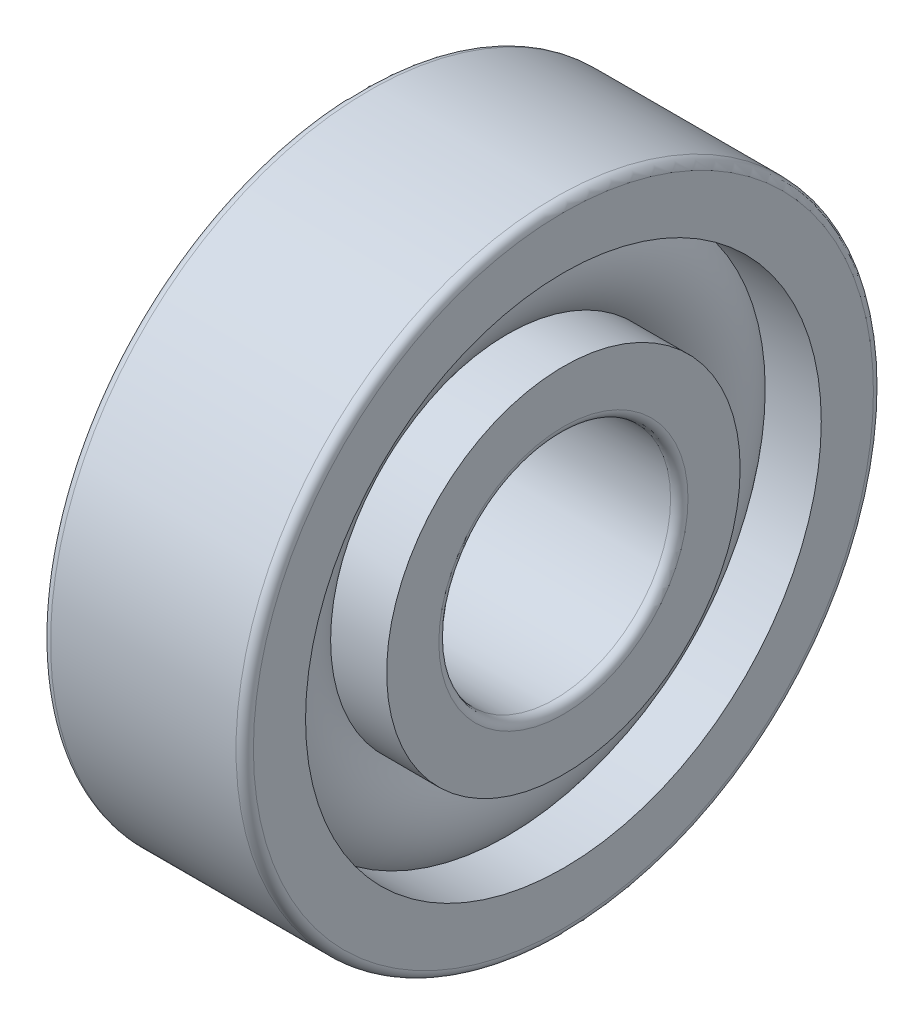
SolidWorks part; units mm, degrees
ref_plane "Plane1" through (0, 0, 0) normal (0, 0, 1) x (1, 0, 0)
ref_plane "Plane2" through (0, 0, 0) normal (0, 1, 0) x (1, 0, 0)
ref_plane "Plane3" through (0, 0, 0) normal (1, 0, 0) x (0, 0, -1)
sketch "Clipboard" plane through (0, 0, 0) normal (0, 0, 1) x (1, 0, 0)
  line L0 (-10, 0) -> (10, 0) construction
  line L1 (0, 0) -> (22.3471, -0.7804)
  line L2 (0, 0) -> (7.4954, 0.2617)
  line L3 (0, 0) -> (22.3471, -0.7804)
  line L4 (0, 0) -> (-22.3573, -0.3902)
  dimension "BallCLRad" = 7.5
  dimension "Count" = 2
  dimension "Show_count" = 2
  dimension "Max_count" = 2
  dimension "Min_count" = 1
sketch "CagSpiSke" plane through (0, 0, 0) normal (0, 0, 1) x (1, 0, 0)
  line L0 (0.21, 7.15) -> (0.21, 7.85)
  line L1 (0.21, 7.85) -> (-0.21, 7.85)
  line L2 (-0.21, 7.85) -> (-0.21, 7.15)
  line L3 (-0.21, 7.15) -> (0.21, 7.15)
  line L4 (-20.6375, 0) -> (20.6375, 0) construction
  line L5 (0, 0) -> (0, 23.7692) construction
  dimension "Thickness" = 0.42
  dimension "OD" = 15.7
  dimension "ID" = 14.3
revolve "CageSpine" add sketch "CagSpiSke" angle 0.001 about L4 reverse direction yes
ref_axis "Axis1" through (-50, 0, 0) along (1, 0, 0)
sketch "CagBalSke" plane through (0, 0, 0) normal (0, 0, 1) x (1, 0, 0)
  line L0 (-2.31, 7.5) -> (2.31, 7.5)
  line L1 (-1.905, 7.5) -> (1.905, 7.5) construction
  line L2 (-10, 0) -> (10, 0) construction
  line L3 (0, 0) -> (0, 24) construction
  arc A0 (2.31, 7.5) -> (-2.31, 7.5) centre (0, 7.5) cw
  dimension "CageWallOD" = 4.62
  dimension "BallCLRad" = 7.5
revolve "CageBall" [suppressed] add sketch "CagBalSke" angle 360 about L1 reverse direction yes
pattern_circular "CageBalls" [suppressed] count 2 every 180 about axis through (-50, 0, 0) along (1, 0, 0)
sketch "CagTrmODSke" plane through (0, 0, 0) normal (0, 0, 1) x (1, 0, 0)
  line L0 (2.311, 7.85) -> (2.311, 9.811)
  line L1 (2.311, 9.811) -> (-2.311, 9.811)
  line L2 (-2.311, 9.811) -> (-2.311, 7.85)
  line L3 (-2.311, 7.85) -> (2.311, 7.85)
  line L4 (-20.6375, 0) -> (20.6375, 0) construction
  line L5 (0, 0) -> (0, 25) construction
  dimension "Width" = 4.622
  dimension "ID" = 15.7
  dimension "OD" = 19.622
revolve "CageTrimOD" [suppressed] cut sketch "CagTrmODSke" angle 360 about L4 reverse direction yes
sketch "CagTrmIDSke" plane through (0, 0, 0) normal (0, 0, 1) x (1, 0, 0)
  line L0 (2.311, 5.191) -> (2.311, 7.15)
  line L1 (2.311, 7.15) -> (-2.311, 7.15)
  line L2 (-2.311, 7.15) -> (-2.311, 5.191)
  line L3 (-2.311, 5.191) -> (2.311, 5.191)
  line L4 (-20.6375, 0) -> (20.6375, 0) construction
  line L5 (0, 0) -> (0, 25) construction
  dimension "ID" = 10.382
  dimension "OD" = 14.3
  dimension "Width" = 4.622
revolve "CageTrimID" [suppressed] cut sketch "CagTrmIDSke" angle 360 about L4 reverse direction yes
sketch "BalSimSke" plane through (0, 0, 0) normal (0, 0, 1) x (1, 0, 0)
  line L0 (-10, 0) -> (10, 0) construction
  line L1 (-10, 7.5) -> (10, 7.5) construction
  line L2 (0, 0) -> (0, 23) construction
  circle A0 centre (0, 7.5) radius 2.1
  dimension "Ball_diameter" = 4.2
  dimension "BallCLRad" = 7.5
revolve "BallsSimplified" add sketch "BalSimSke" angle 360 about L0
sketch "BalDetSke" plane through (0, 0, 0) normal (0, 0, 1) x (1, 0, 0)
  line L0 (-2.1, 7.5) -> (2.1, 7.5)
  line L1 (-1.905, 7.5) -> (1.905, 7.5) construction
  line L2 (0, 0) -> (0, 25) construction
  arc A0 (2.1, 7.5) -> (-2.1, 7.5) centre (0, 7.5) cw
  dimension "Ball_diameter" = 4.2
  dimension "BallCLRad" = 7.5
revolve "BallDetailed" [suppressed] add sketch "BalDetSke" angle 360 about L1 reverse direction yes
sketch "InnRacSke" plane through (0, 0, 0) normal (0, 0, 1) x (1, 0, 0)
  line L0 (-1.5315, 6.1) -> (-3.5, 6.1)
  line L1 (-3.5, 6.1) -> (-3.5, 4.3)
  line L2 (-3.2, 4) -> (3.2, 4)
  line L3 (3.5, 4.3) -> (3.5, 6.1)
  line L4 (3.5, 6.1) -> (1.5315, 6.1)
  line L5 (-20.6375, 0) -> (20.6375, 0) construction
  line L6 (0, 0) -> (0, 30) construction
  arc A0 (-3.5, 4.3) -> (-3.2, 4) centre (-3.2, 4.3) ccw
  arc A1 (3.2, 4) -> (3.5, 4.3) centre (3.2, 4.3) ccw
  arc A2 (1.5315, 6.1) -> (-1.5315, 6.1) centre (0, 7.5) cw
  dimension "Fillet_radius" = 0.3
  dimension "Ball_diameter" = 4.15
  dimension "ID" = 8
  dimension "OD" = 12.2
  dimension "Width" = 7
  dimension "BallCLRad" = 7.5
revolve "InnerRace" add sketch "InnRacSke" angle 360 about L5 reverse direction yes
sketch "OutRacSke" plane through (0, 0, 0) normal (0, 0, 1) x (1, 0, 0)
  line L0 (-1.5315, 8.9) -> (-3.5, 8.9)
  line L1 (-3.5, 8.9) -> (-3.5, 10.7)
  line L2 (-3.2, 11) -> (3.2, 11)
  line L3 (3.5, 10.7) -> (3.5, 8.9)
  line L4 (3.5, 8.9) -> (1.5315, 8.9)
  line L5 (-20.6375, 0) -> (20.6375, 0) construction
  line L6 (0, 0) -> (0, 30) construction
  arc A0 (-3.5, 10.7) -> (-3.2, 11) centre (-3.2, 10.7) cw
  arc A1 (3.2, 11) -> (3.5, 10.7) centre (3.2, 10.7) cw
  arc A2 (1.5315, 8.9) -> (-1.5315, 8.9) centre (0, 7.5) ccw
  dimension "Fillet_radius" = 0.3
  dimension "Ball_diameter" = 4.15
  dimension "OD" = 22
  dimension "ID" = 17.8
  dimension "Width" = 7
  dimension "BallCLRad" = 7.5
revolve "OuterRace" add sketch "OutRacSke" angle 360 about L5 reverse direction yes
pattern_circular "BallsDetailed" [suppressed] count 2 every 180 about axis through (-50, 0, 0) along (1, 0, 0)
equation "\"BallCLRad@Clipboard\" = ( \"OD@OutRacSke\" + \"ID@InnRacSke\" ) / 4"
equation "\"BallCLRad@BalSimSke\" = \"BallCLRad@Clipboard\""
equation "\"BallCLRad@BalDetSke\" = \"BallCLRad@Clipboard\""
equation "\"BallCLRad@InnRacSke\" = \"BallCLRad@Clipboard\""
equation "\"BallCLRad@OutRacSke\" = \"BallCLRad@Clipboard\""
equation "\"Ball_diameter@InnRacSke\" = \"Ball_diameter@BalDetSke\" - 0.05"
equation "\"Ball_diameter@OutRacSke\" = \"Ball_diameter@BalDetSke\" - 0.05"
equation "\"Ball_diameter@BalSimSke\" = \"Ball_diameter@BalDetSke\""
equation "\"Width@OutRacSke\" = \"Width@InnRacSke\""
equation "\"Fillet_radius@OutRacSke\" = \"Fillet_radius@InnRacSke\""
equation "\"Max_count@Clipboard\" = int( 3.14159265 / atn(( \"Ball_diameter@BalDetSke\" / 2) / sqr( \"BallCLRad@Clipboard\"  *  \"BallCLRad@Clipboard\" - ( \"Ball_diameter@BalDetSke\" / 2) *  ( \"Ball_diameter@BalDetSke\" / 2))))"
equation "\"Max_count@Clipboard\" = ((sgn( \"Max_count@Clipboard\" - \"Count@Clipboard\" )-1)*( \"Max_count@Clipboard\" - \"Count@Clipboard\" ))/-2+ \"Count@Clipboard\""
equation "\"Count@BallsDetailed\" = int( \"Show_count@Clipboard\" ) "
equation "\"Count@BallsDetailed\" = ((sgn( \"Count@BallsDetailed\" - \"Max_count@Clipboard\" )-1)*( \"Count@BallsDetailed\" - \"Max_count@Clipboard\" ))/-2+ \"Max_count@Clipboard\""
equation "\"Count@BallsDetailed\" = ((sgn( \"Count@BallsDetailed\" - \"Min_count@Clipboard\" )+1)*( \"Count@BallsDetailed\" - \"Min_count@Clipboard\"))/2 +\"Min_count@Clipboard\""
equation "\"Angle@BallsDetailed\" = 360.0 / \"Max_count@Clipboard\""
equation "\"BallCLRad@CagBalSke\" = \"BallCLRad@Clipboard\""
equation "\"Count@CageBalls\" = \"Count@BallsDetailed\""
equation "\"Angle@CageBalls\" = \"Angle@BallsDetailed\""
equation "\"Angle@CageSpine\" =  \"Angle@CageBalls\" * ( \"Count@CageBalls\" -1 + int( \"Count@CageBalls\" / \"Max_count@Clipboard\" ) )  + 0.001 -  int( \"Count@CageBalls\" / \"Max_count@Clipboard\" ) * 0.001"
equation "\"Angle@CageSpine\" =  \"Angle@CageSpine\" * int( \"Min_count@Clipboard\" / 2) + int(1 / \"Min_count@Clipboard\")  * 0.001"
equation "\"CageWallOD@CagBalSke\" =  \"Ball_diameter@BalDetSke\" * 1.1"
equation "\"Thickness@CagSpiSke\" =  \"Ball_diameter@BalDetSke\" * 0.1"
equation "\"OD@CagTrmODSke\" = \"BallCLRad@Clipboard\" * 2 + \"CageWallOD@CagBalSke\" + 0.002"
equation "\"ID@CagTrmODSke\" = \"BallCLRad@Clipboard\" * 2 + \"Ball_diameter@BalDetSke\" / 6"
equation "\"OD@CagTrmIDSke\" = \"BallCLRad@Clipboard\" * 2 - \"Ball_diameter@BalDetSke\" / 6"
equation "\"ID@CagTrmIDSke\" = \"BallCLRad@Clipboard\" * 2 - \"CageWallOD@CagBalSke\" + 0.002"
equation "\"OD@CagSpiSke\" = \"ID@CagTrmODSke\""
equation "\"ID@CagSpiSke\" = \"OD@CagTrmIDSke\""
equation "\"Width@CagTrmODSke\" = \"CageWallOD@CagBalSke\" + 0.002"
equation "\"Width@CagTrmIDSke\" = \"CageWallOD@CagBalSke\" + 0.002"
